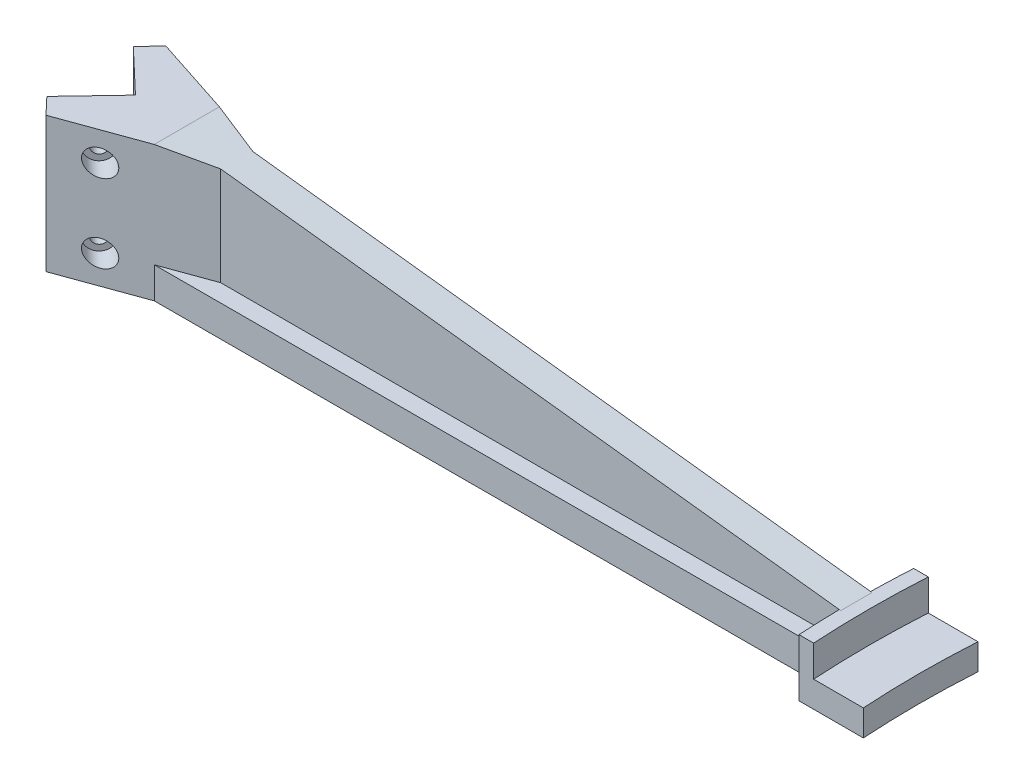
SolidWorks part; units mm, degrees
ref_plane "Front Plane" through (0, 0, 0) normal (0, 0, 1) x (1, 0, 0)
ref_plane "Top Plane" through (0, 0, 0) normal (0, 1, 0) x (1, 0, 0)
ref_plane "Right Plane" through (0, 0, 0) normal (1, 0, 0) x (0, 0, -1)
sketch "Sketch2" plane through (0, 0, 0) normal (0, 1, 0) x (1, 0, 0)
  line L0 (0, 0) -> (-276.0246, 0) construction
  line L1 (0, 0) -> (135.9511, 0) construction
  line L2 (-276.0246, 0) -> (-292.5966, 15.7434)
  line L3 (-292.5966, 15.7434) -> (-286.5108, 22.1496)
  line L4 (-286.5108, 22.1496) -> (-276.0246, 12.1877)
  line L5 (-276.0246, 12.1877) -> (-276.0246, 0)
  line L14 (0.6536, 22) -> (25.3402, 22)
  line L15 (0.6536, -22) -> (25.3402, -22)
  line L16 (25.3402, 22) -> (25.3402, -22) construction
  line L34 (-276.0246, 0) -> (-292.5966, -17.4443)
  line L49 (-292.5966, -17.4443) -> (-286.5108, -23.8504)
  line L50 (-286.5108, -23.8504) -> (-276.0246, -12.8123)
  line L51 (-276.0246, -12.8123) -> (-276.0246, 0)
  line L52 (-276.0246, 12.1877) -> (0.2109, 12.5)
  line L53 (-276.0246, -12.8123) -> (0.2109, -12.5)
  line L54 (0.2109, -12.5) -> (0.2109, 12.5) construction
  line L55 (-276.0246, 12.1877) -> (-276.0246, 24.2548) construction
  line L56 (-276.0246, -12.8123) -> (-276.0246, -19.1381)
  line L58 (-286.5108, 22.1496) -> (-256.0246, 12.2103)
  line L62 (-286.5108, -23.8504) -> (-256.0246, -12.7897)
  line L63 (-256.0246, 12.2103) -> (-256.0246, -12.7897)
  line L64 (-256.0246, -12.7897) -> (-219.7315, 0.3778)
  line L65 (-256.0246, 12.2103) -> (-219.7315, 0.3778)
  arc A0 (0.6536, 22) -> (0.6536, -22) centre (370.6, 0) ccw
  arc A1 (6.2636, 22) -> (6.2636, -22) centre (370.6, 0) ccw
  arc A2 (25.3402, 22) -> (25.3402, -22) centre (370.6, 0) ccw
  point P12 (-219.4633, -12.8783)
  point P25 (0, 0)
  point P27 (0, 0)
  point P28 (-148.6931, -34.0679)
  point P32 (5.6, 0)
  dimension "D2" = 365
  dimension "D3" = 5.6
  dimension "D4" = 19.04
  dimension "D7" = 25
  dimension "D5" = 133.531
  dimension "D6" = 136.469
  dimension "D8" = 25
  dimension "D9" = 44
  dimension "D10" = 20
  dimension "D18" = 46
  dimension "D19" = 281.6246
extrude "Boss-Extrude2" add sketch "Sketch2" against normal blind 12 contours A0 L52 L53 | L53 L52 | L53 | L52 | A1 L14 A0 L15 | L50 L51 L34 L49 | L5 L4 L3 L2 | L65 L63 L64 region at (-282.9032, 0, -12.1717) region at (-282.9032, 0, 13.1665) region at (-266.0246, 0, 0.301) region at (-272.8533, 0, -15.5159) region at (-272.8533, 0, 16.4841) region at (-243.9269, 0, 0.0672) region at (-119.1345, 0, 0.1509) region at (3.0196, 0, 0)
extrude "Boss-Extrude3" add sketch "Sketch2<5>" along normal blind 10 from surface contours A2 L14 A1 L15 region at (15.3473, 0, 0) starting at face at (-148.6736, -12, 0.3062)
sketch "Sketch2<5>" plane through (0, 0, 0) normal (0, 1, 0) x (1, 0, 0) same geometry as "Sketch2"
extrude "Boss-Extrude4" add sketch "Sketch2<6>" along normal blind 22 from surface contours A1 L14 A0 L15 region at (3.0196, 0, 0) starting at face at (-145.7416, -12, 0.3062)
sketch "Sketch2<6>" plane through (0, 0, 0) normal (0, 1, 0) x (1, 0, 0) same geometry as "Sketch2"
extrude "Boss-Extrude7" add sketch "Sketch2<9>" along normal blind 40 contours L63 L52 L5 L51 L53 | L5 L4 L3 L2 | L58 L4 L52 | L50 L51 L34 L49 | L50 L62 L53 | L65 L63 L64 region at (-282.9032, 0, -12.1717) region at (-282.9032, 0, 13.1665) region at (-266.0246, 0, 0.301) region at (-272.8533, 0, -15.5159) region at (-272.8533, 0, 16.4841) region at (-243.9269, 0, 0.0672)
sketch "Sketch2<9>" plane through (0, 0, 0) normal (0, 1, 0) x (1, 0, 0) same geometry as "Sketch2"
sketch "Sketch4" plane through (0, 0, 0) normal (0, 0, 1) x (1, 0, 0)
  line L2 (-292.5966, -12) -> (-292.5966, 40) construction
  line L5 (0.6536, 10) -> (-256.0246, 40)
  line L6 (-286.5108, 40) -> (-219.7315, 40) construction
  line L8 (-276.0246, 0) -> (0.2109, 0) construction
  line L9 (-256.0246, 0) -> (0.6536, 0)
  line L10 (0.6536, 0) -> (0.6536, 10)
  line L11 (0.6536, -12) -> (0.6536, 10) construction
  line L12 (0.6536, 10) -> (0, 10) construction
  line L13 (-256.0246, 40) -> (-256.0246, 0)
  dimension "D1" = 36.572
extrude "Boss-Extrude17" add sketch "Sketch4" along normal blind 6 and the other way blind 6
sketch "Sketch5" plane through (0, 0, 0) normal (0, 0, 1) x (1, 0, 0)
  line L0 (0.6536, 10) -> (-256.0246, 40) construction
  line L1 (0.6536, 10) -> (-256.0246, 40)
extrude "Cut-Extrude-Thin1" cut sketch "Sketch5" against normal through all and the other way through all thin contours L1 thin type one direction wall 10
sketch "Sketch6" plane through (-145.0852, 0, -137.8309) normal (-0.725, 0, -0.6887) x (-0.6887, 0, 0.725)
  line L0 (200.1118, 29) -> (200.1118, -1) construction
  line L1 (190.1118, 40) -> (214.1728, 40) construction
  line L2 (190.1118, 40) -> (210.1118, 40)
  line L3 (190.1118, 40) -> (190.1118, -12)
  line L4 (190.1118, -12) -> (210.1118, -12)
  line L5 (210.1118, 40) -> (210.1118, -12)
  line L6 (190.1118, 40) -> (210.1118, -12) construction
  line L7 (190.1118, -12) -> (210.1118, 40) construction
  line L8 (190.1118, -12) -> (190.1118, 40) construction
  line L9 (190.1118, -12) -> (214.1728, -12) construction
  circle A0 centre (200.1118, 29) radius 5
  circle A1 centre (200.1118, -1) radius 5
  circle A2 centre (200.1118, 29) radius 2.75
  circle A3 centre (200.1118, -1) radius 2.75
  point P3 (200.1118, 14)
  point P6 (200.1118, 14)
  dimension "D2" = 10
  dimension "D3" = 5.5
  dimension "D1" = 20
  dimension "D4" = 30
extrude "Cut-Extrude1" cut sketch "Sketch6" against normal through all from offset 8 contours A0 | A1 offset against normal yes
extrude "Cut-Extrude2" cut sketch "Sketch6<4>" against normal through all both and the other way through all contours A2 | A3
sketch "Sketch6<4>" plane through (-145.0852, 0, -137.8309) normal (-0.725, 0, -0.6887) x (-0.6887, 0, 0.725) same geometry as "Sketch6"
mirror "Mirror1" about plane through (0, 0, 0) normal (0, 0, 1) of "Cut-Extrude1", "Cut-Extrude2"
